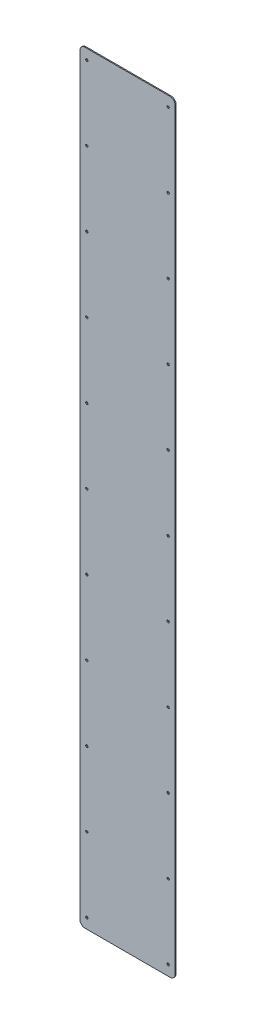
SolidWorks part; units mm, degrees
material "ASTM A36 Steel"
ref_plane "Front Plane" through (0, 0, 0) normal (0, 0, 1) x (1, 0, 0)
ref_plane "Top Plane" through (0, 0, 0) normal (0, 1, 0) x (1, 0, 0)
ref_plane "Right Plane" through (0, 0, 0) normal (1, 0, 0) x (0, 0, -1)
sketch "Sketch1" plane through (0, 0, 0) normal (0, 0, 1) x (1, 0, 0)
  line L0 (13.6, 1480) -> (13.6, 1334) construction
  line L1 (10, 0) -> (177.2, 0)
  line L2 (0, 10) -> (0, 1490)
  line L3 (10, 1500) -> (177.2, 1500)
  line L4 (187.2, 10) -> (187.2, 1490)
  arc A0 (0, 10) -> (10, 0) centre (10, 10) ccw
  arc A1 (187.2, 10) -> (177.2, 0) centre (177.2, 10) cw
  arc A2 (177.2, 1500) -> (187.2, 1490) centre (177.2, 1490) cw
  arc A3 (0, 1490) -> (10, 1500) centre (10, 1490) cw
  circle A4 centre (13.6, 1480) radius 2.25
  circle A5 centre (173.6, 1480) radius 2.25
  circle A6 centre (173.6, 1334) radius 2.25
  circle A7 centre (173.6, 1188) radius 2.25
  circle A8 centre (173.6, 1042) radius 2.25
  circle A9 centre (173.6, 896) radius 2.25
  circle A10 centre (173.6, 750) radius 2.25
  circle A11 centre (173.6, 604) radius 2.25
  circle A12 centre (173.6, 458) radius 2.25
  circle A13 centre (173.6, 312) radius 2.25
  circle A14 centre (173.6, 166) radius 2.25
  circle A15 centre (173.6, 20) radius 2.25
  circle A16 centre (13.6, 1334) radius 2.25
  circle A17 centre (13.6, 1188) radius 2.25
  circle A18 centre (13.6, 1042) radius 2.25
  circle A19 centre (13.6, 896) radius 2.25
  circle A20 centre (13.6, 750) radius 2.25
  circle A21 centre (13.6, 604) radius 2.25
  circle A22 centre (13.6, 458) radius 2.25
  circle A23 centre (13.6, 312) radius 2.25
  circle A24 centre (13.6, 166) radius 2.25
  circle A25 centre (13.6, 20) radius 2.25
  point P7 (0, 0)
  point P10 (187.2, 0)
  point P15 (0, 1500)
  dimension "D3" = 10
  dimension "D4" = 4.5
  dimension "D1" = 1500
  dimension "D2" = 187.2
  dimension "D5" = 13.6
  dimension "D6" = 20
  dimension "D9" = 146
  dimension "D10" = 13.6
  dimension "D7" = 2
  dimension "D8" = 11
base flange "Base-Flange1" sketch "Sketch1" thickness 2 reverse thickness direction no parameters "D1"=0.7366
sketch "Bend-Lines1" [suppressed] plane through (0, 0, 0) normal (0, 1, 0) x (1, 0, 0)
sketch "Bounding-Box1" [suppressed] plane through (0, 0, 0) normal (0, 1, 0) x (1, 0, 0)
sheet metal parameters "Sheet-Metal1" thickness 2 parameters "D1"=0.7366
flat pattern "Flat-Pattern1" [suppressed]
sketch "Bend-Lines2" plane through (0, 0, 0) normal (0, 1, 0) x (1, 0, 0)
sketch3d "Bounding-Box2" [suppressed]
  line L0 (177.2, -10, 0) -> (177.2, 1490, 0) construction
  line L1 (-10, -10, 0) -> (-10, 1490, 0) construction
  line L2 (177.2, -10, 0) -> (-10, -10, 0) construction
  line L3 (177.2, 1490, 0) -> (-10, 1490, 0) construction
